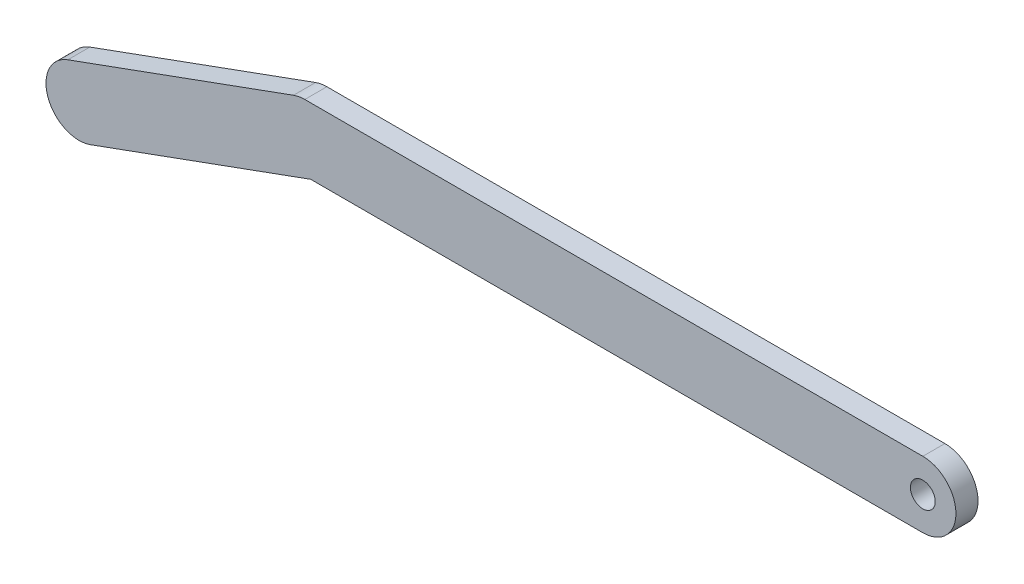
SolidWorks part; units mm, degrees
ref_plane "Front Plane" through (0, 0, 0) normal (0, 0, 1) x (1, 0, 0)
ref_plane "Top Plane" through (0, 0, 0) normal (0, 1, 0) x (1, 0, 0)
ref_plane "Right Plane" through (0, 0, 0) normal (1, 0, 0) x (0, 0, -1)
sketch "Sketch1" plane through (0, 0, 0) normal (0, 0, 1) x (1, 0, 0)
  line L0 (44.45, 0) -> (-44.45, 0) construction
  line L1 (44.45, -4.7625) -> (-44.45, -4.7625)
  line L2 (44.45, 4.7625) -> (-44.45, 4.7625)
  line L3 (-44.45, 0) -> (-76.9172, -11.8171) construction
  line L4 (-42.8211, -4.4753) -> (-75.2883, -16.2924)
  line L5 (-46.0789, 4.4753) -> (-78.546, -7.3418)
  arc A0 (44.45, -4.7625) -> (44.45, 4.7625) centre (44.45, 0) ccw
  arc A1 (-44.45, 4.7625) -> (-44.45, -4.7625) centre (-44.45, 0) ccw
  arc A2 (-42.8211, -4.4753) -> (-46.0789, 4.4753) centre (-44.45, 0) ccw
  arc A3 (-78.546, -7.3418) -> (-75.2883, -16.2924) centre (-76.9172, -11.8171) ccw
  point P2 (0, 0)
  point P10 (-60.6836, -5.9085)
  dimension "D2" = 4.7625
  dimension "D3" = 4.7625
  dimension "D1" = 88.9
  dimension "D4" = 160
extrude "Boss-Extrude1" add sketch "Sketch1" along normal blind 3.175 contours L4 A2 A1 L1 | L5 A3 L4 L1 A1 | A2 L4 L1 A0 L2 region at (3.7427, 0.0002, 0) region at (-64.201, -7.1882, 0) region at (-44.4495, -0.0027, 0)
hole_wizard "9/64 (0.14063) Diameter Hole1" positions "Sketch4" profile "Sketch3" hole size "9/64" standard "ANSI Inch" end condition through all
sketch "Sketch4" plane through (0, 0, 3.175) normal (0, 0, 1) x (1, 0, 0)
  point P0 (44.45, 0)
sketch "Sketch3" plane through (44.45, 0, 3.175) normal (1, 0, 0) x (0, -1, 0)
  line L0 (0, 0) -> (0, 3.175)
  line L1 (0, 3.175) -> (1.786, 3.175)
  line L2 (1.786, 3.175) -> (1.786, 0)
  line L5 (1.786, 0) -> (0, 0)
  line L11 (0, -6.35) -> (0, 107.95) construction
  dimension "Thru Hole Dia." = 3.572
  dimension "Thru Hole Depth" = 3.175
